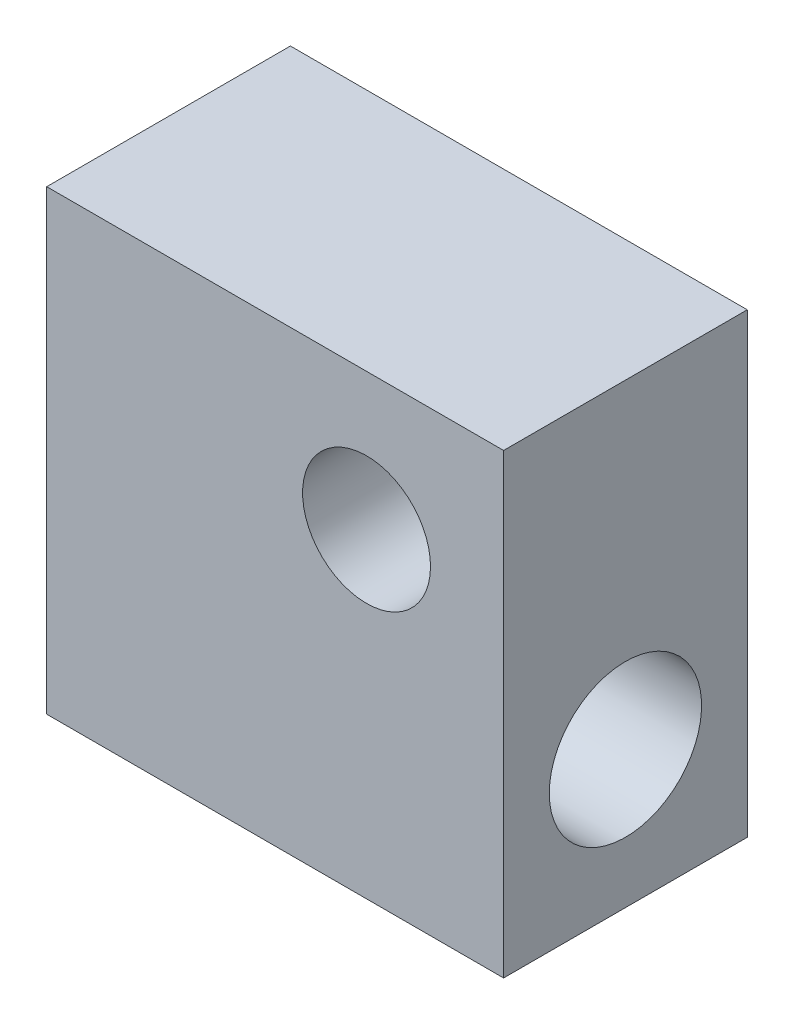
SolidWorks part; units mm, degrees
ref_plane "Front Plane" through (0, 0, 0) normal (0, 0, 1) x (1, 0, 0)
ref_plane "Top Plane" through (0, 0, 0) normal (0, 1, 0) x (1, 0, 0)
ref_plane "Right Plane" through (0, 0, 0) normal (1, 0, 0) x (0, 0, -1)
sketch "Sketch1" plane through (0, 0, 0) normal (0, 0, 1) x (1, 0, 0)
  line L1 (0, 0) -> (15, 0)
  line L2 (0, 0) -> (0, 15)
  line L3 (0, 15) -> (15, 15)
  line L4 (15, 0) -> (15, 15)
  dimension "D1" = 15
  dimension "D2" = 15
extrude "Boss-Extrude1" add sketch "Sketch1" along normal blind 8
hole_wizard "Tap Drill for M5x0.8 Tap1" positions "Sketch3" profile "Sketch2" hole size "M5x0.8" standard "Ansi Metric" end condition through all
sketch "Sketch3" plane through (0, 0, 8) normal (0, 0, 1) x (1, 0, 0)
  line L0 (15, 0) -> (15, 15) construction
  line L1 (15, 15) -> (0, 15) construction
  point P0 (10.5, 10.5)
  dimension "D1" = 4.5
  dimension "D2" = 4.5
sketch "Sketch2" plane through (10.5, 10.5, 8) normal (1, 0, 0) x (0, -1, 0)
  line L0 (0, 0) -> (0, 8)
  line L1 (0, 8) -> (2.1, 8)
  line L2 (2.1, 8) -> (2.1, 0)
  line L5 (2.1, 0) -> (0, 0)
  line L11 (0, -6.35) -> (0, 107.95) construction
  dimension "Thru Hole Dia." = 4.2
  dimension "Thru Hole Depth" = 8
ref_axis "Axis1" through (10.5, 10.5, 0) along (0, 0, 1)
hole_wizard "Ø5.0 (5) Diameter Hole1" positions "Sketch5" profile "Sketch4" hole size "Ø5.0" standard "Ansi Metric" end condition through all
sketch "Sketch5" plane through (0, 0, 0) normal (-1, 0, 0) x (0, 0, 1)
  line L0 (4, 0) -> (4, 7.9761) construction
  line L1 (8, 0) -> (0, 0) construction
  point P0 (4, 4.5)
  dimension "D1" = 4.5
sketch "Sketch4" plane through (0, 4.5, 4) normal (0, 1, 0) x (0, 0, 1)
  line L0 (0, 0) -> (0, 15)
  line L1 (0, 15) -> (2.5, 15)
  line L2 (2.5, 15) -> (2.5, 0)
  line L5 (2.5, 0) -> (0, 0)
  line L11 (0, -6.35) -> (0, 107.95) construction
  dimension "Thru Hole Dia." = 5
  dimension "Thru Hole Depth" = 15
hole_wizard "Ø2.5 (2.5) Diameter Hole1" positions "Sketch9" profile "Sketch8" hole size "Ø2.5" standard "Ansi Metric"
sketch "Sketch9" plane through (0, 0, 0) normal (-1, 0, 0) x (0, 0, 1)
  line L0 (4, 15) -> (4, 0) construction
  line L1 (8, 15) -> (0, 15) construction
  line L3 (8, 0) -> (0, 0) construction
  line L4 (0, 10.5) -> (8, 10.5) construction
  point P0 (4, 10.5)
sketch "Sketch8" plane through (0, 10.5, 4) normal (0, 1, 0) x (0, 0, 1)
  line L0 (0, 0) -> (0, 6.8011)
  line L1 (0, 6.8011) -> (1.25, 6.05)
  line L2 (1.25, 6.05) -> (1.25, 0)
  line L5 (1.25, 0) -> (0, 0)
  line L10 (0, 6.8011) -> (-1.25, 6.05) construction
  line L11 (0, -6.35) -> (0, 107.95) construction
  dimension "Hole Dia." = 2.5
  dimension "Hole Depth" = 6.05
  dimension "Drill Angle" = 118
